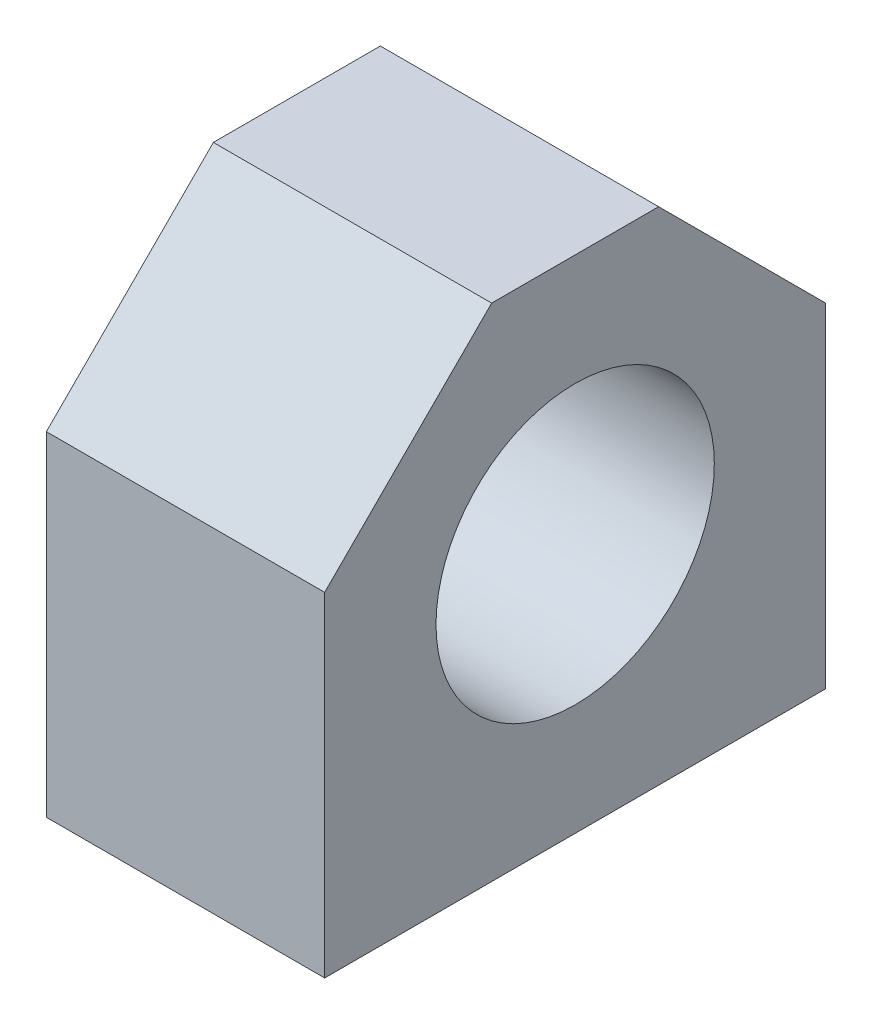
SolidWorks part; units mm, degrees
material "6061 Alloy"
ref_plane "Front Plane" through (0, 0, 0) normal (0, 0, 1) x (1, 0, 0)
ref_plane "Top Plane" through (0, 0, 0) normal (0, 1, 0) x (1, 0, 0)
ref_plane "Right Plane" through (0, 0, 0) normal (1, 0, 0) x (0, 0, -1)
sketch "Sketch2" plane through (0, 0, 0) normal (1, 0, 0) x (0, 0, -1)
  line L1 (0, 0) -> (57.15, 0)
  line L2 (0, 0) -> (0, 57.15)
  line L3 (0, 57.15) -> (57.15, 57.15)
  line L4 (57.15, 0) -> (57.15, 57.15)
  dimension "D1" = 57.15
extrude "Boss-Extrude2" add sketch "Sketch2" along normal blind 31.75
sketch "Sketch3" plane through (31.75, 0, 0) normal (1, 0, 0) x (0, 0, -1)
  line L0 (0, 57.15) -> (57.15, 0) construction
  circle A0 centre (28.575, 28.575) radius 15.875
  dimension "D1" = 31.75
extrude "Cut-Extrude1" cut sketch "Sketch3" against normal through all
sketch "Sketch4" plane through (0, 0, 0) normal (-1, 0, 0) x (0, 0, 1)
  line L0 (-28.575, 46.0375) -> (-28.575, 11.1125) construction
  line L1 (-36.1884, 46.0375) -> (-20.9616, 46.0375)
  line L2 (-20.9616, 11.1125) -> (-36.1884, 11.1125)
  circle A0 centre (-28.575, 28.575) radius 15.875 construction
  arc A1 (-36.1884, 46.0375) -> (-36.1884, 11.1125) centre (-28.575, 28.575) ccw
  arc A2 (-20.9616, 46.0375) -> (-20.9616, 11.1125) centre (-28.575, 28.575) cw
  point P2 (-28.575, 28.575)
  dimension "D2" = 19.05
  dimension "D1" = 34.925
extrude "Cut-Extrude2" cut sketch "Sketch4" against normal blind 2.54
fillet "Fillet1" radius 3.175 4 edges at (1.27, 11.1125, -36.1884) (1.27, 11.1125, -20.9616) (1.27, 46.0375, -20.9616) (1.27, 46.0375, -36.1884)
chamfer "Chamfer1" distance 19.05 distance2 19.05 2 edges at (15.875, 57.15, -57.15) (15.875, 57.15, 0)
